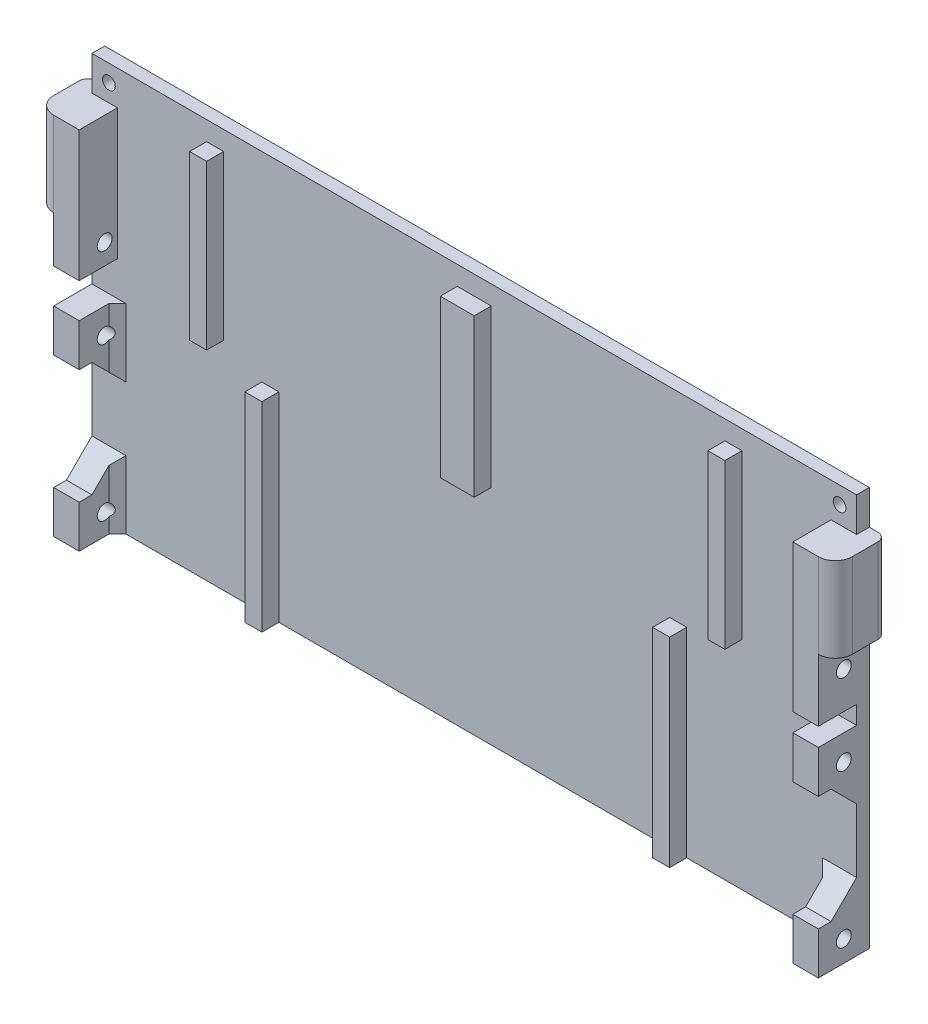
SolidWorks part; units mm, degrees
material "АБС-2020, черный"
ref_plane "Спереди" through (0, 0, 0) normal (0, 0, 1) x (1, 0, 0)
ref_plane "Сверху" through (0, 0, 0) normal (0, 1, 0) x (1, 0, 0)
ref_plane "Справа" through (0, 0, 0) normal (1, 0, 0) x (0, 0, -1)
other "Configuration Table"
sketch "Эскиз1" plane through (0, 0, 0) normal (0, 0, 1) x (1, 0, 0)
  line L1 (0, 0) -> (180, 0)
  line L2 (0, 0) -> (0, -94)
  line L3 (0, -94) -> (180, -94)
  line L4 (180, 0) -> (180, -94)
  dimension "D1" = 94
  dimension "D2" = 180
extrude "Бобышка-Вытянуть1" add sketch "Эскиз1" along normal blind 3
sketch "Эскиз2" plane through (0, 0, 3) normal (0, 0, 1) x (1, 0, 0)
  line L0 (0, 0) -> (0, -94) construction
  line L1 (0, -94) -> (6, -94)
  line L2 (0, -94) -> (0, -84)
  line L3 (0, -84) -> (6, -84)
  line L4 (6, -94) -> (6, -84)
  line L5 (180, -94) -> (174, -94)
  line L6 (180, -94) -> (180, -84)
  line L7 (180, -84) -> (174, -84)
  line L8 (174, -94) -> (174, -84)
  line L9 (0, -47) -> (6, -47)
  line L10 (0, -47) -> (0, -57)
  line L11 (0, -57) -> (6, -57)
  line L12 (6, -47) -> (6, -57)
  line L13 (180, -94) -> (180, 0) construction
  line L14 (180, -47) -> (174, -47)
  line L15 (180, -47) -> (180, -57)
  line L16 (180, -57) -> (174, -57)
  line L17 (174, -47) -> (174, -57)
  line L18 (0, -94) -> (180, -94) construction
  line L19 (180, 0) -> (0, 0) construction
  line L20 (180, -8.1) -> (174, -8.1)
  line L21 (180, -8.1) -> (180, -42.7)
  line L22 (180, -42.7) -> (174, -42.7)
  line L23 (174, -8.1) -> (174, -42.7)
  line L24 (0, -8.1) -> (6, -8.1)
  line L25 (0, -8.1) -> (0, -38.854)
  line L26 (0, -38.854) -> (6, -38.854)
  line L27 (6, -8.1) -> (6, -38.854)
  dimension "D1" = 10
  dimension "D2" = 6
  dimension "D3" = 10
  dimension "D4" = 6
  dimension "D5" = 47
  dimension "D6" = 6
  dimension "D7" = 6
  dimension "D8" = 47
  dimension "D9" = 10
  dimension "D10" = 10
  dimension "D11" = 4.3
  dimension "D12" = 8.1
  dimension "D13" = 8.1
extrude "Бобышка-Вытянуть2" add sketch "Эскиз2" along normal blind 9
chamfer "Фаска2" distance 6 angle 45 2 edges at (3, -57, 3) (177, -57, 3)
chamfer "Фаска1" distance 6 angle 45 2 edges at (3, -84, 3) (177, -84, 3)
sketch "Эскиз3" plane through (180, 0, 0) normal (1, 0, 0) x (0, 0, -1)
  line L0 (0, -94) -> (0, 0) construction
  line L1 (-12, -94) -> (0, -94) construction
  line L2 (-3, 0) -> (0, 0) construction
  circle A0 centre (-6, -89) radius 1.75
  circle A1 centre (-6, -53) radius 1.75
  circle A2 centre (-6, -34) radius 1.75
  dimension "D1" = 3.5
  dimension "D4" = 3.5
  dimension "D7" = 3.5
  dimension "D2" = 6
  dimension "D3" = 5
  dimension "D5" = 36
  dimension "D6" = 34
extrude "Вырез-Вытянуть1" cut sketch "Эскиз3" against normal through all
sketch "Эскиз4" plane through (0, 0, 3) normal (0, 0, 1) x (1, 0, 0)
  line L0 (0, -84) -> (0, -94) construction
  line L1 (180, -94) -> (180, -84) construction
  line L2 (180, 0) -> (0, 0) construction
  circle A0 centre (4, -4) radius 1.5
  circle A1 centre (176, -4) radius 1.5
  dimension "D7" = 3
  dimension "D1" = 4
  dimension "D2" = 4
  dimension "D3" = 4
extrude "Вырез-Вытянуть2" cut sketch "Эскиз4" against normal through all
sketch "Эскиз5" plane through (0, 0, 3) normal (0, 0, 1) x (1, 0, 0)
  line L0 (6, -94) -> (174, -94) construction
  line L1 (40, -47) -> (44, -47)
  line L2 (40, -47) -> (40, -94)
  line L3 (40, -94) -> (44, -94)
  line L4 (44, -47) -> (44, -94)
  line L5 (180, -78) -> (180, -63) construction
  line L6 (136, -47) -> (140, -47)
  line L7 (136, -47) -> (136, -94)
  line L8 (136, -94) -> (140, -94)
  line L9 (140, -47) -> (140, -94)
  line L10 (0, -63) -> (0, -78) construction
  line L11 (180, 0) -> (0, 0) construction
  line L13 (27, -4.5) -> (27, -43)
  line L14 (27, -43) -> (31, -43)
  line L15 (31, -4.5) -> (31, -43)
  line L16 (6, -47) -> (0, -47) construction
  line L18 (149, -4.5) -> (149, -43)
  line L19 (149, -43) -> (153, -43)
  line L20 (153, -4.5) -> (153, -43)
  line L21 (27, -4.5) -> (31, -4.5)
  line L22 (149, -4.5) -> (153, -4.5)
  line L23 (0, 0) -> (0, -8.1) construction
  line L24 (180, -47) -> (180, -42.7) construction
  line L26 (86, -4.5) -> (94, -4.5)
  line L27 (86, -4.5) -> (86, -41.5)
  line L28 (86, -41.5) -> (94, -41.5)
  line L29 (94, -4.5) -> (94, -41.5)
  dimension "D12" = 8
  dimension "D1" = 4
  dimension "D2" = 4
  dimension "D3" = 40
  dimension "D4" = 40
  dimension "D5" = 4
  dimension "D6" = 4
  dimension "D7" = 27
  dimension "D8" = 4
  dimension "D9" = 4.5
  dimension "D10" = 4
  dimension "D11" = 27
  dimension "D13" = 55
  dimension "D14" = 55
extrude "Бобышка-Вытянуть3" add sketch "Эскиз5" along normal blind 4
chamfer "Фаска3" distance 2 angle 45 4 edges at (174, -86, 3) (174, -55, 3) (6, -86, 3) (6, -55, 3)
sketch "Эскиз6" plane through (180, 0, 0) normal (1, 0, 0) x (0, 0, -1)
  line L0 (0, -94) -> (0, 0) construction
  line L1 (-12, -8.1) -> (0, -8.1)
  line L2 (-12, -8.1) -> (-12, -28)
  line L3 (-12, -28) -> (0, -28)
  line L4 (0, -8.1) -> (0, -28)
  line L5 (-3, 0) -> (0, 0) construction
  dimension "D1" = 28
  dimension "D2" = 8.1
extrude "Бобышка-Вытянуть4" add sketch "Эскиз6" along normal blind 4
fillet "Скругление1" radius 4 1 edges at (184, -18.05, 12)
sketch "Эскиз7" plane through (0, 0, 0) normal (-1, 0, 0) x (0, 0, 1)
  line L0 (12, -8.1) -> (12, -38.854) construction
  line L1 (0, -8.1) -> (12, -8.1)
  line L2 (0, -8.1) -> (0, -28)
  line L3 (0, -28) -> (12, -28)
  line L4 (12, -8.1) -> (12, -28)
  line L5 (3, 0) -> (0, 0) construction
  dimension "D1" = 28
extrude "Бобышка-Вытянуть5" add sketch "Эскиз7" along normal blind 4
fillet "Скругление2" radius 4 1 edges at (-4, -18.05, 12)
fillet "Скругление3" radius 2 2 edges at (184, -18.05, 0) (-4, -18.05, 0)
